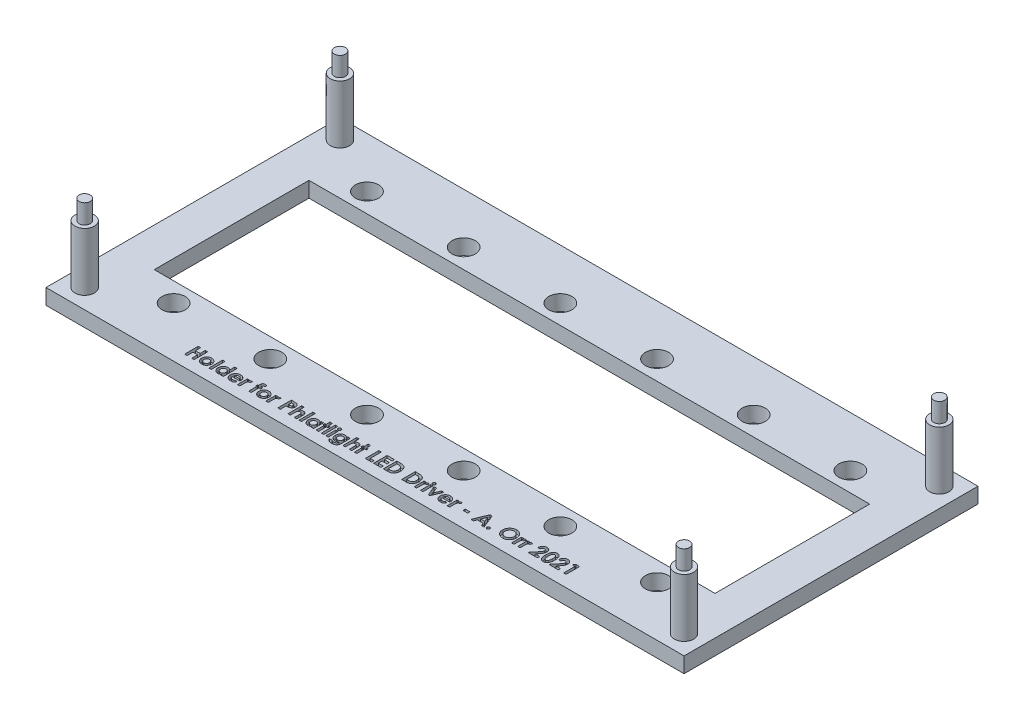
SolidWorks part; units mm, degrees
ref_plane "Front Plane" through (0, 0, 0) normal (0, 0, 1) x (1, 0, 0)
ref_plane "Top Plane" through (0, 0, 0) normal (0, 1, 0) x (1, 0, 0)
ref_plane "Right Plane" through (0, 0, 0) normal (1, 0, 0) x (0, 0, -1)
sketch "Sketch1" plane through (0, 0, 0) normal (0, 1, 0) x (1, 0, 0)
  line L1 (-81.1284, 43.8167) -> (83.8716, 43.8167)
  line L2 (-81.1284, 43.8167) -> (-81.1284, -32.1833)
  line L3 (-81.1284, -32.1833) -> (83.8716, -32.1833)
  line L4 (83.8716, 43.8167) -> (83.8716, -32.1833)
  dimension "D1" = 165
  dimension "D2" = 76
extrude "Boss-Extrude1" add sketch "Sketch1" along normal blind 4
sketch "Sketch2" plane through (0, 4, 0) normal (0, 1, 0) x (1, 0, 0)
  line L0 (-81.1284, 43.8167) -> (-81.1284, -32.1833) construction
  line L1 (-81.1284, -32.1833) -> (83.8716, -32.1833) construction
  line L2 (1.3716, 43.8167) -> (1.3716, -32.1833) construction
  line L3 (83.8716, 43.8167) -> (-81.1284, 43.8167) construction
  line L4 (-81.1284, 5.8167) -> (83.8716, 5.8167) construction
  line L5 (83.8716, -32.1833) -> (83.8716, 43.8167) construction
  circle A0 centre (-76.1284, -27.1833) radius 2.5
  circle A1 centre (78.8716, -27.1833) radius 2.5
  circle A2 centre (78.8716, 38.8167) radius 2.5
  circle A3 centre (-76.1284, 38.8167) radius 2.5
  dimension "D1" = 5
  dimension "D3" = 5
  dimension "D2" = 5
extrude "Boss-Extrude2" add sketch "Sketch2" along normal blind 15
sketch "Sketch3" plane through (0, 19, 0) normal (0, 1, 0) x (1, 0, 0)
  circle A0 centre (78.8716, 38.8167) radius 1.45
  circle A1 centre (-76.1284, -27.1833) radius 1.45
  circle A2 centre (78.8716, -27.1833) radius 1.45
  circle A3 centre (-76.1284, 38.8167) radius 1.45
  dimension "D1" = 2.9
extrude "Boss-Extrude3" add sketch "Sketch3" along normal blind 5
sketch "Sketch4" plane through (0, 4, 0) normal (0, 1, 0) x (1, 0, 0)
  line L0 (83.8716, 43.8167) -> (-81.1284, 43.8167) construction
  line L1 (-11.1284, 30.8167) -> (13.8716, 30.8167) construction
  line L2 (-81.1284, 5.8167) -> (83.8716, 5.8167) construction
  line L3 (-81.1284, 43.8167) -> (-81.1284, -32.1833) construction
  line L4 (83.8716, -32.1833) -> (83.8716, 43.8167) construction
  circle A0 centre (-61.1284, 30.8167) radius 3
  circle A1 centre (-36.1284, 30.8167) radius 3
  circle A2 centre (-11.1284, 30.8167) radius 3
  circle A3 centre (13.8716, 30.8167) radius 3
  circle A4 centre (38.8716, 30.8167) radius 3
  circle A5 centre (63.8716, 30.8167) radius 3
  circle A6 centre (63.8716, -19.1833) radius 3
  circle A7 centre (38.8716, -19.1833) radius 3
  circle A8 centre (13.8716, -19.1833) radius 3
  circle A9 centre (-11.1284, -19.1833) radius 3
  circle A10 centre (-36.1284, -19.1833) radius 3
  circle A11 centre (-61.1284, -19.1833) radius 3
  point P14 (1.3716, 30.8167)
  point P15 (1.3716, 43.8167)
  dimension "D1" = 6
  dimension "D3" = 50
  dimension "D2" = 6
extrude "Cut-Extrude1" cut sketch "Sketch4" against normal through all
sketch "Sketch5" plane through (0, 4, 0) normal (0, 1, 0) x (1, 0, 0)
  line L0 (83.8716, 43.8167) -> (-81.1284, 43.8167) construction
  line L1 (-71.1284, 25.8167) -> (73.8716, 25.8167)
  line L2 (-71.1284, 25.8167) -> (-71.1284, -14.1833)
  line L3 (-71.1284, -14.1833) -> (73.8716, -14.1833)
  line L4 (73.8716, 25.8167) -> (73.8716, -14.1833)
  line L5 (-81.1284, 43.8167) -> (-81.1284, -32.1833) construction
  point P4 (1.3716, 25.8167)
  point P7 (1.3716, 43.8167)
  point P8 (-71.1284, 5.8167)
  point P11 (-81.1284, 5.8167)
  dimension "D1" = 40
  dimension "D2" = 145
extrude "Cut-Extrude2" cut sketch "Sketch5" against normal through all
sketch "Sketch6" plane through (0, 4, 0) normal (0, 1, 0) x (1, 0, 0)
  line L0 (-63.6284, -29.1833) -> (66.3716, -29.1833) construction
  line L1 (-81.1284, -32.1833) -> (83.8716, -32.1833) construction
  text T0 "<b>Holder for Phlatlight LED Driver - A. Orr 2021</b>"
  dimension "D1" = 3
extrude "Cut-Extrude3" cut sketch "Sketch6" against normal blind 1
